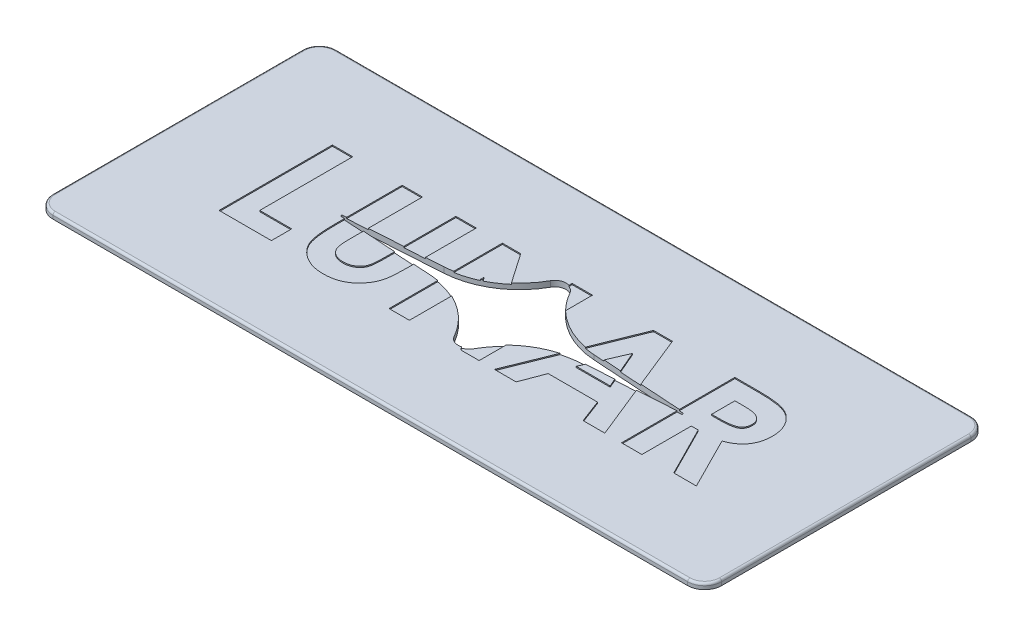
SolidWorks part; units mm, degrees
material "201 Annealed Stainless Steel (SS)"
ref_plane "Front Plane" through (0, 0, 0) normal (0, 0, 1) x (1, 0, 0)
ref_plane "Top Plane" through (0, 0, 0) normal (0, 1, 0) x (1, 0, 0)
ref_plane "Right Plane" through (0, 0, 0) normal (1, 0, 0) x (0, 0, -1)
sketch "Sketch1" plane through (0, 0, 0) normal (0, 1, 0) x (1, 0, 0)
  line L1 (-147.5, 62.5) -> (147.5, 62.5)
  line L2 (-147.5, 62.5) -> (-147.5, -62.5)
  line L3 (-147.5, -62.5) -> (147.5, -62.5)
  line L4 (147.5, 62.5) -> (147.5, -62.5)
  line L5 (-147.5, 62.5) -> (147.5, -62.5) construction
  line L6 (-147.5, -62.5) -> (147.5, 62.5) construction
  point P0 (0, 0)
  dimension "D1" = 295
  dimension "D2" = 125
extrude "Boss-Extrude1" add sketch "Sketch1" along normal blind 2.5
fillet "Fillet1" radius 7.5 4 edges at (147.5, 1.25, 62.5) (-147.5, 1.25, 62.5) (147.5, 1.25, -62.5) (-147.5, 1.25, -62.5)
fillet "Fillet2" radius 1 8 edges at (145.3033, 2.5, -60.3033) (147.5, 2.5, 0) (145.3033, 2.5, 60.3033) (0, 2.5, 62.5) (-145.3033, 2.5, 60.3033) (-147.5, 2.5, 0) (-145.3033, 2.5, -60.3033) (0, 2.5, -62.5)
sketch "Sketch4" plane through (0, 2.5, 0) normal (0, 1, 0) x (1, 0, 0)
  line L0 (-75.0254, 0.3951) -> (-33.074, 3.09)
  line L1 (-75, 0) -> (75, 0) construction
  line L2 (-75, 1.25) -> (75, 1.25) construction
  line L3 (-75, -1.25) -> (75, -1.25) construction
  line L4 (0, 34.3443) -> (0, 0) construction
  line L5 (75.0254, 0.3951) -> (33.074, 3.09)
  line L6 (-23.8422, 0) -> (49433.0468, 0) construction
  line L7 (-75.0254, -0.3951) -> (-33.074, -3.09)
  line L8 (75.0254, -0.3951) -> (33.074, -3.09)
  arc A0 (-75, 1.25) -> (-75, -1.25) centre (-75, 0) ccw construction
  arc A1 (75, -1.25) -> (75, 1.25) centre (75, 0) ccw construction
  circle A2 centre (-75, 0) radius 0.3959
  arc A3 (-33.074, 3.09) -> (0, 34.3443) centre (-35.3573, 38.6332) ccw
  circle A4 centre (75, 0) radius 0.3959
  arc A5 (33.074, 3.09) -> (0, 34.3443) centre (35.3573, 38.6332) cw
  arc A6 (-33.074, -3.09) -> (0, -34.3443) centre (-35.3573, -38.6332) cw
  arc A7 (33.074, -3.09) -> (0, -34.3443) centre (35.3573, -38.6332) ccw
  arc A8 (-4.2367, 21.3115) -> (4.2367, 21.3115) centre (0, 18.9533) cw
  arc A9 (-4.2367, -21.3115) -> (4.2367, -21.3115) centre (0, -18.9533) ccw
  point P4 (0, 0)
  point P6 (0, 0)
  point P36 (-75, 0.9775)
  point P37 (-24.749, 1.1011)
  point P38 (-75.0556, 0.6487)
  point P39 (-22.1261, 3.0552)
  point P40 (0, 0)
  point P41 (0, 19.1149)
  point P42 (-0.1488, 19.0941)
  point P43 (0, 18.9742)
  point P44 (0, 0)
  point P45 (-27.3523, 3.4576)
  point P46 (0, 34.3443)
  dimension "D1" = 150
  dimension "D2" = 2.5
extrude "Cut-Extrude4" cut sketch "Sketch4" against normal blind 10 contours A6 A9 A7 L8 A4 L5 A5 A8 A3 L0 A2 L7 | A2 | A4 region at (0, 2.5, 0)
sketch "Sketch3" plane through (0, 2.5, 0) normal (0, 1, 0) x (1, 0, 0)
  line L1 (-110, -25) -> (110, -25) construction
  line L2 (-110, -25) -> (-110, 25) construction
  line L3 (-110, 25) -> (110, 25) construction
  line L4 (110, -25) -> (110, 25) construction
  text T0 "LUNAR" font "Century Gothic" height 50
  point P4 (-110, 0)
  point P6 (0, 25)
  dimension "D1" = 220
  dimension "D2" = 50
extrude "Cut-Extrude3" cut sketch "Sketch3" against normal blind 0.5
